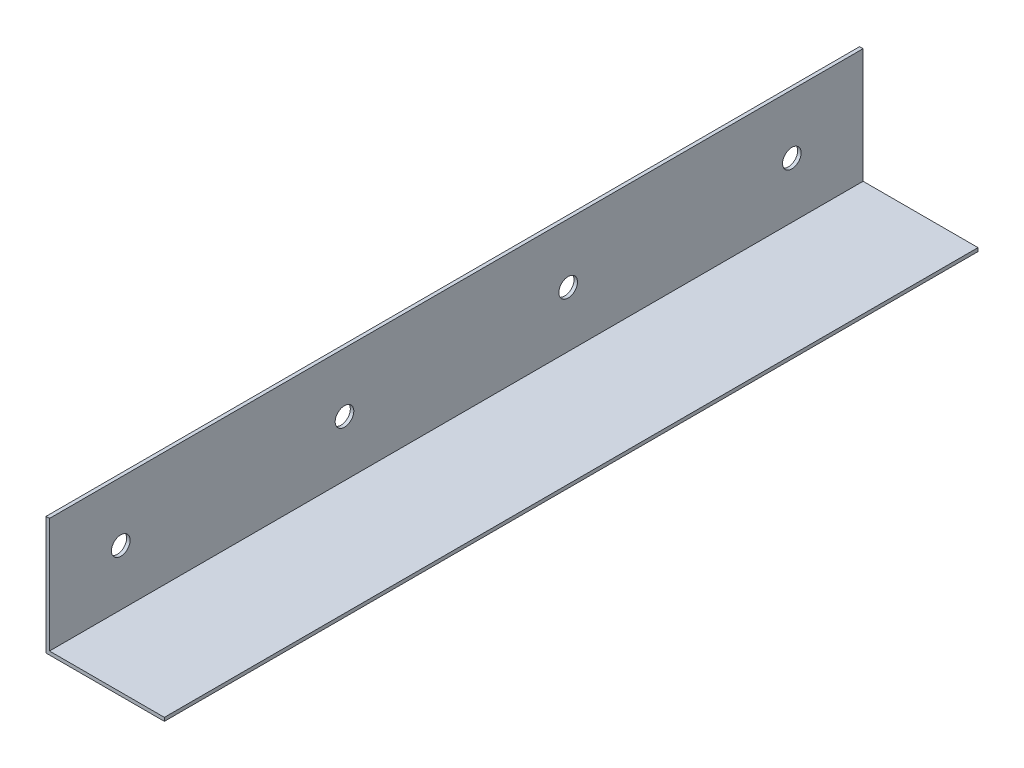
SolidWorks part; units mm, degrees
material "AISI 1015 Acero estirado en frío (SS)"
ref_plane "Alzado" through (0, 0, 0) normal (0, 0, 1) x (1, 0, 0)
ref_plane "Planta" through (0, 0, 0) normal (0, 1, 0) x (1, 0, 0)
ref_plane "Vista lateral" through (0, 0, 0) normal (1, 0, 0) x (0, 0, -1)
sketch "Croquis1" plane through (0, 0, 0) normal (0, 0, 1) x (1, 0, 0)
  line L0 (0, 0) -> (0, 50.8)
  line L1 (0, 0) -> (50.8, 0)
  line L2 (1.5, 1.5) -> (50.8, 1.5)
  line L3 (1.5, 1.5) -> (1.5, 50.8)
  line L4 (1.5, 50.8) -> (0, 50.8)
  line L5 (50.8, 1.5) -> (50.8, 0)
  dimension "D1" = 50.8
  dimension "D2" = 1.5
extrude "Saliente-Extruir1" add sketch "Croquis1" along normal blind 349.2
sketch "Croquis2" plane through (0, 0, 0) normal (-1, 0, 0) x (0, 0, 1)
  line L0 (349.2, 25.4) -> (-34.0342, 25.4) construction
  line L1 (349.2, 50.8) -> (349.2, 0) construction
  line L2 (174.6, 0) -> (174.6, 64.0617) construction
  line L3 (349.2, 0) -> (0, 0) construction
  circle A0 centre (126.6, 25.4) radius 4
  circle A1 centre (222.6, 25.4) radius 4
  circle A2 centre (30.6, 25.4) radius 4
  circle A3 centre (318.6, 25.4) radius 4
  dimension "D1" = 8
  dimension "D2" = 48
  dimension "D3" = 48
  dimension "D4" = 96
  dimension "D5" = 96
extrude "Cortar-Extruir1" cut sketch "Croquis2" against normal blind 2
